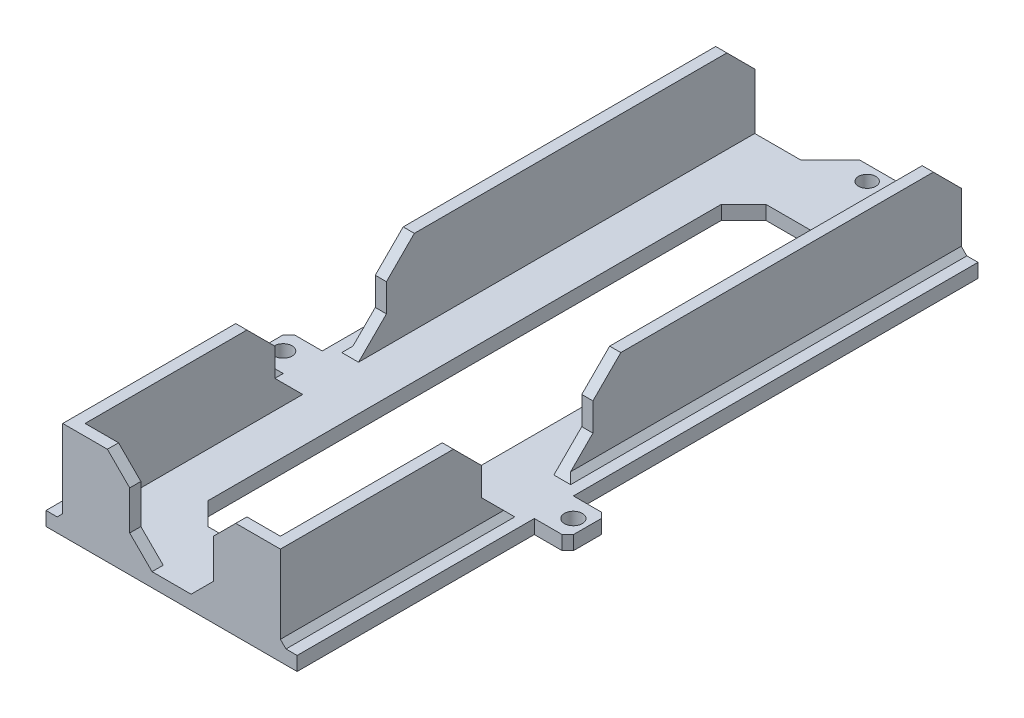
SolidWorks part; units mm, degrees
ref_plane "Front Plane" through (0, 0, 0) normal (0, 0, 1) x (1, 0, 0)
ref_plane "Top Plane" through (0, 0, 0) normal (0, 1, 0) x (1, 0, 0)
ref_plane "Right Plane" through (0, 0, 0) normal (1, 0, 0) x (0, 0, -1)
sketch "Sketch1" plane through (0, 0, 0) normal (0, 1, 0) x (1, 0, 0)
  line L1 (0, 0) -> (45, 0)
  line L2 (0, 0) -> (0, 122)
  line L3 (0, 122) -> (45, 122)
  line L4 (45, 0) -> (45, 122)
  dimension "D1" = 122
  dimension "D2" = 45
extrude "Boss-Extrude1" add sketch "Sketch1" along normal blind 2.5
sketch "Sketch3" plane through (0, 2.5, 0) normal (0, 1, 0) x (1, 0, 0)
  line L0 (45, 122) -> (0, 122) construction
  line L1 (3, 122) -> (5, 122)
  line L2 (3, 122) -> (3, 0)
  line L3 (3, 0) -> (5, 0)
  line L4 (5, 122) -> (5, 0)
  line L5 (0, 0) -> (45, 0) construction
  line L6 (0, 122) -> (0, 0) construction
  line L7 (40, 122) -> (42, 122)
  line L8 (40, 122) -> (40, 0)
  line L9 (40, 0) -> (42, 0)
  line L10 (42, 122) -> (42, 0)
  line L11 (45, 0) -> (45, 122) construction
  line L13 (5, 0) -> (40, 0)
  line L14 (5, 0) -> (5, 2)
  line L15 (5, 2) -> (40, 2)
  line L16 (40, 0) -> (40, 2)
  line M8 (0, 0) -> (45, 0)
  line M10 (45, 122) -> (0, 122)
  dimension "D1" = 3
  dimension "D2" = 3
  dimension "D3" = 2
  dimension "D4" = 2
  dimension "D5" = 2
extrude "Boss-Extrude2" add sketch "Sketch3" along normal blind 15 contours L4 L2 M10 M8 | L15 L4 L8 M8 | L9 L10 L7 L8 region at (4, 2.5, -61) region at (22.5, 2.5, -1)
ref_plane "Plane1" through (0, 0, 0) normal (0, 1, 0) x (1, 0, 0)
sketch "Sketch4" plane through (0, 0, 0) normal (0, 1, 0) x (1, 0, 0)
  line L0 (45, 0) -> (45, 46) construction
  line L1 (45, 0) -> (45, 122) construction
  line L2 (45, 46) -> (0, 46) construction
  line L3 (0, 122) -> (0, 0) construction
  line L4 (22.5, 46) -> (22.5, 68.7913) construction
  line L5 (6, 42.5) -> (-6, 42.5)
  line L6 (6, 42.5) -> (6, 49.5)
  line L7 (6, 49.5) -> (-6, 49.5)
  line L8 (-6, 42.5) -> (-6, 49.5)
  line L9 (6, 42.5) -> (-6, 49.5) construction
  line L10 (6, 49.5) -> (-6, 42.5) construction
  line L11 (39, 49.5) -> (51, 49.5)
  line L12 (51, 42.5) -> (51, 49.5)
  line L13 (39, 42.5) -> (51, 42.5)
  line L14 (39, 42.5) -> (39, 49.5)
  dimension "D1" = 12
  dimension "D2" = 7
extrude "Boss-Extrude3" add sketch "Sketch4" along normal blind 2.5
sketch "Sketch6" plane through (0, 2.5, 0) normal (0, 1, 0) x (1, 0, 0)
  line L0 (22.5, 122) -> (22.5, 2) construction
  line L1 (40, 122) -> (5, 122) construction
  line L2 (5, 2) -> (40, 2) construction
  line L3 (3, 122) -> (3, 0) construction
  line L4 (13, 12) -> (32, 12)
  line L5 (13, 12) -> (13, 112)
  line L6 (13, 112) -> (32, 112)
  line L7 (32, 12) -> (32, 112)
  line L8 (13, 12) -> (32, 112) construction
  line L9 (13, 112) -> (32, 12) construction
  point P6 (22.5, 62)
  dimension "D1" = 10
  dimension "D2" = 10
extrude "Cut-Extrude2" cut sketch "Sketch6" against normal blind 12.5
fillet "Fillet1" radius 4 4 edges at (13, 1.25, -12) (32, 1.25, -12) (13, 1.25, -112) (32, 1.25, -112) profile chamfer
sketch "Sketch8" plane through (51, 0, 0) normal (1, 0, 0) x (0, 0, -1)
  line L0 (46, 2.5) -> (46, 17.5) construction
  line L1 (42.5, 2.5) -> (49.5, 2.5) construction
  line L2 (122, 17.5) -> (0, 17.5) construction
  line L3 (122, 2.5) -> (0, 2.5) construction
  line L4 (36, 17.5) -> (56, 17.5)
  line L5 (36, 17.5) -> (36, 2.5)
  line L6 (36, 2.5) -> (56, 2.5)
  line L7 (56, 17.5) -> (56, 2.5)
  line L8 (36, 17.5) -> (56, 2.5) construction
  line L9 (36, 2.5) -> (56, 17.5) construction
  point P6 (46, 10)
  dimension "D1" = 20
extrude "Cut-Extrude3" cut sketch "Sketch8" against normal blind 58.5
fillet "Fillet2" radius 5 10 edges at (4, 2.5, -56) (4, 2.5, -36) (41, 2.5, -36) (41, 2.5, -56) (41, 17.5, -56) (41, 17.5, -36) (4, 17.5, -56) (4, 17.5, -36) (4, 17.5, -122) (41, 17.5, -122) profile chamfer
sketch "Sketch9" plane through (0, 0, 0) normal (0, -1, 0) x (1, 0, 0)
  line L0 (51, -42.5) -> (51, -49.5) construction
  line L2 (51, -49.5) -> (45, -49.5) construction
  line L3 (48, -49.5) -> (22.5, 0) construction
  line L4 (0, 0) -> (45, 0) construction
  line L5 (22.5, 0) -> (22.5, -112) construction
  line L6 (17, -112) -> (28, -112) construction
  circle A0 centre (48.5, -46) radius 1.6
  circle A1 centre (-3.5, -46) radius 1.6
  dimension "D1" = 3.2
  dimension "D2" = 2.5
extrude "Cut-Extrude4" cut sketch "Sketch9" against normal blind 58.5
sketch "Sketch10" plane through (0, 0, 0) normal (0, 1, 0) x (1, 0, 0)
  line L0 (40, 122) -> (5, 122) construction
  line L1 (18.5, 122) -> (26.5, 122)
  line L2 (18.5, 122) -> (18.5, 127.2825)
  line L3 (18.5, 127.2825) -> (26.5, 127.2825)
  line L4 (26.5, 122) -> (26.5, 127.2825)
  line L5 (0, 122) -> (0, 49.5) construction
  line L6 (45, 49.5) -> (45, 122) construction
  line L7 (22.5, 127.2825) -> (22.5, 122) construction
  circle A0 centre (22.5, 124.6412) radius 1.55
  dimension "D4" = 3.1
  dimension "D1" = 18.5
  dimension "D2" = 18.5
  dimension "D3" = 8
extrude "Boss-Extrude4" add sketch "Sketch10" against normal blind 5 and the other way blind 2.5 separate body
sketch "Sketch11" plane through (18.5, 0, 0) normal (-1, 0, 0) x (0, 0, 1)
  line L0 (-119.5, 0) -> (-122.0284, -2.5)
  line L1 (39.6554, 0) -> (-39.6554, 0) construction
  line L2 (-122.0284, -2.5) -> (-122, 0)
  line L3 (-122, 2.5) -> (-122, -5) construction
  line L4 (-122, 0) -> (-119.5, 0)
  dimension "D1" = 2.5
  dimension "D2" = 2.5
extrude "Boss-Extrude5" add sketch "Sketch11" against normal blind 8
sketch "Sketch12" plane through (0, 2.5, 0) normal (0, 1, 0) x (1, 0, 0)
  line L0 (18.5, 127.2825) -> (18.5, 122)
  line L1 (18.5, 122) -> (13.22, 122)
  line L2 (18.5, 122) -> (5, 122) construction
  line L3 (13.22, 122) -> (18.5, 127.2825)
  line L4 (22.5, 127.2825) -> (22.5, 122) construction
  line L5 (26.5, 127.2825) -> (18.5, 127.2825) construction
  line L6 (26.5, 122) -> (31.78, 122)
  line L7 (26.5, 127.2825) -> (26.5, 122)
  line L8 (31.78, 122) -> (26.5, 127.2825)
  dimension "D1" = 5.28
extrude "Boss-Extrude6" add sketch "Sketch12" against normal blind 2.5
fillet "Fillet3" radius 2.5 2 edges at (26.5, 0, -123.3912) (18.5, 0, -123.3912) profile chamfer
sketch "Sketch13" plane through (0, 0, 0) normal (0, 0, 1) x (1, 0, 0)
  line L0 (22.5, 17.5) -> (22.5, 0) construction
  line L1 (3, 17.5) -> (42, 17.5) construction
  line L2 (0, 0) -> (45, 0) construction
  line L4 (15, 32.5) -> (30, 32.5)
  line L5 (15, 32.5) -> (15, 2.5)
  line L6 (15, 2.5) -> (30, 2.5)
  line L7 (30, 32.5) -> (30, 2.5)
  line L8 (15, 32.5) -> (30, 2.5) construction
  line L9 (15, 2.5) -> (30, 32.5) construction
  dimension "D1" = 15
extrude "Cut-Extrude5" cut sketch "Sketch13" against normal blind 6.5
fillet "Fillet4" radius 4 4 edges at (30, 2.5, -1) (15, 2.5, -1) (15, 17.5, -1) (30, 17.5, -1) profile chamfer
fillet "Fillet5" radius 1 4 edges at (42, 2.5, -86.5) (42, 2.5, -20.5) (3, 2.5, -20.5) (3, 2.5, -86.5) profile chamfer
fillet "Fillet7" radius 1 4 edges at (51, 1.25, -42.5) (51, 1.25, -49.5) (-6, 1.25, -42.5) (-6, 1.25, -49.5) profile chamfer
